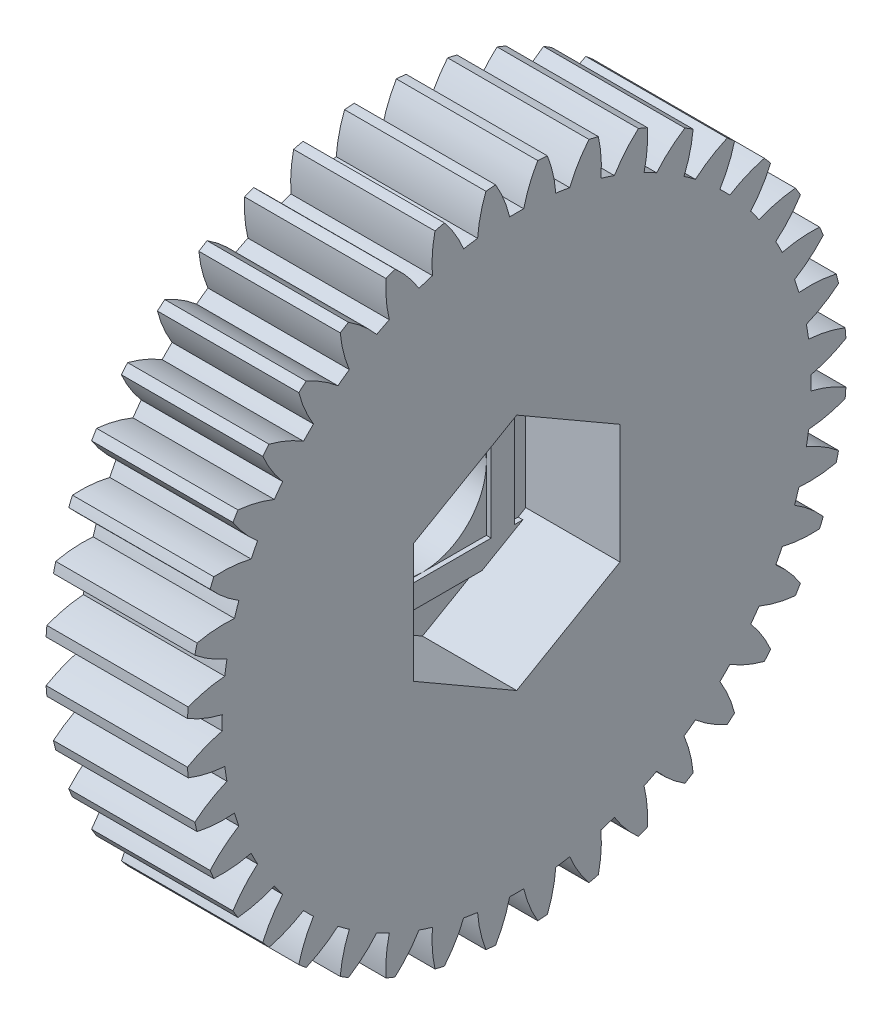
SolidWorks part; units mm, degrees
ref_plane "Plane1" through (0, 0, 0) normal (0, 0, 1) x (1, 0, 0)
ref_plane "Plane2" through (0, 0, 0) normal (0, 1, 0) x (1, 0, 0)
ref_plane "Plane3" through (0, 0, 0) normal (1, 0, 0) x (0, 0, -1)
sketch "HoldingSke" plane through (0, 0, 0) normal (0, 1, 0) x (1, 0, 0)
  line L0 (0, 0) -> (0.766, -0.6428)
  line L1 (-15, 0) -> (100, 0) construction
  line L2 (0, 0) -> (-2.1039, 2.3779)
  line L3 (0, 0) -> (-11.863, 4.5341)
  line L4 (0, 0) -> (6.6156, 5.5511)
  line L5 (0, 0) -> (-46.8476, -17.4728)
  line L6 (0, 0) -> (-7.4607, -5.0337)
  line L7 (-2.1039, 2.3779) -> (8.6586, 51.2059)
  line L8 (-76.2, 54.61) -> (-75.5, 54.61)
  line L9 (-71.009, 38.7566) -> (-53.1078, 45.2721)
  line L10 (-76.2, 71.12) -> (104.1128, 71.12)
  line L11 (0, 0) -> (-9, 0)
  line L12 (-76.2, 101.6) -> (-76.162, 101.6)
  line L13 (24.9733, 27.94) -> (52.9518, 28.4284)
  line L14 (24.9733, 27.94) -> (24.9743, 27.94)
  line L15 (24.9733, 27.94) -> (100.4006, 29.5858)
  line L16 (-63.627, -1) -> (-12.827, -1)
  circle A0 centre (0, 0) radius 2
  circle A1 centre (0, 0) radius 18.749
  circle A2 centre (0, 0) radius 37.5
  circle A3 centre (0, 0) radius 2
  dimension "MHD" = 37.498
  dimension "Hub_dia" = 75
  dimension "Bore" = 4
  dimension "MBD" = 4
  dimension "Num_teeth" = 40
  dimension "Pitch" = 1
  dimension "Overall_len" = 50
  dimension "Show_teeth" = 40
  dimension "Thickness" = 9
  dimension "OAL" = 50.0001
  dimension "T_dim" = 0.7
  dimension "Ap" = 20
  dimension "H" = 19.05
  dimension "Pitch_radius" = 180.3128
  dimension "Width" = 9
  dimension "Backlash" = 0.038
  dimension "Addendum_fac" = 1
  dimension "Dedendum_fac" = 1.25
  dimension "Clearance_fac" = 0.25
  dimension "Dedendum_add" = 0.001
  dimension "Module" = 1
sketch "BasProSke" plane through (0, 0, 0) normal (0, 1, 0) x (1, 0, 0)
  line L0 (-10, 0) -> (60, 0) construction
  line L1 (0, 0) -> (0, 21)
  line L2 (0, 0) -> (9, 0)
  line L3 (9, 0) -> (9, 21)
  line L4 (9, 21) -> (0, 21)
  dimension "Thickness" = 9
  dimension "Diameter" = 42
revolve "Base-Revolve" add sketch "BasProSke" angle 360 about L0
sketch "TooCutSke" plane through (0, 0, 0) normal (1, 0, 0) x (0, 0, -1)
  line L1 (0, 0) -> (0, 107) construction
  line L2 (0, 0) -> (-0.8517, 19.9819) construction
  line L3 (0, 0) -> (-3.1363, 39.8509) construction
  line L4 (-0.8517, 19.9819) -> (-1.5682, 19.9255) construction
  arc A0 (0.4487, 18.7436) -> (-0.4487, 18.7436) centre (0, 0) ccw
  arc A1 (1.3547, 20.9817) -> (-1.3547, 20.9817) centre (0, 0) ccw
  circle A2 centre (0, 0) radius 20 construction
  circle A3 centre (0, 0) radius 18.7939 construction
  arc A4 (-0.4487, 18.7436) -> (-1.3547, 20.9817) centre (-8.2322, 16.895) ccw
  arc A5 (1.3547, 20.9817) -> (0.4487, 18.7436) centre (8.2322, 16.895) ccw
  dimension "Root_dia" = 37.498
  dimension "Overcut_dia" = 42.0508
  dimension "Pitch_dia" = 40
  dimension "Base_dia" = 37.5877
  dimension "Flank_rad" = 8
  dimension "Half_ang" = 4.5
  dimension "Half_CT" = 0.7187
extrude "ToothCut" cut sketch "TooCutSke" along normal through all
fillet "Breaks" [suppressed] radius 0.02 tangent propagation no
fillet "RootFillets" [suppressed] radius 0.251
pattern_circular "TeethCuts" count 40 every 9 about axis through (-10, 0, 0) along (1, 0, 0) of "ToothCut", "RootFillets", "Breaks"
sketch "HubNeaOneSke" plane through (0, 0, 0) normal (-1, 0, 0) x (0, 0, 1)
  circle A0 centre (0, 0) radius 18.749
  dimension "Diameter" = 37.498
extrude "HubNearOne" [suppressed] add sketch "HubNeaOneSke" along normal blind 41.0001
sketch "HubNeaBotSke" plane through (0, 0, 0) normal (-1, 0, 0) x (0, 0, 1)
  circle A0 centre (0, 0) radius 18.749
  dimension "Diameter" = 37.498
extrude "HubNearBoth" [suppressed] add sketch "HubNeaBotSke" along normal blind 20.5001
ref_plane "FarPln" through (9, 0, 0) normal (1, 0, 0) x (0, 0, -1)
sketch "HubFarSke" plane through (9, 0, 0) normal (1, 0, 0) x (0, 0, -1)
  circle A0 centre (0, 0) radius 18.749
  dimension "Diameter" = 37.498
extrude "HubFar" [suppressed] add sketch "HubFarSke" along normal blind 20.5001
sketch "BorSke" plane through (0, 0, 0) normal (1, 0, 0) x (0, 0, -1)
  circle A0 centre (0, 0) radius 2
  dimension "Diameter" = 4
extrude "Bore" cut sketch "BorSke" along normal mid plane 100.0002
sketch "KeySke" plane through (0, 0, 0) normal (1, 0, 0) x (0, 0, -1)
  line L0 (-0.8, 0) -> (-0.8, 2.7)
  line L1 (-0.8, 2.7) -> (0.8, 2.7)
  line L2 (0.8, 2.7) -> (0.8, 0)
  line L3 (0, 0) -> (0, 34) construction
  line L4 (-0.8, 0) -> (0.8, 0)
  dimension "Offset" = 2.7
  dimension "Width" = 1.6
extrude "Keyway" [suppressed] cut sketch "KeySke" along normal mid plane 100.0002
pattern_circular "Keyway2" [suppressed] count 2 every 90 about axis through (-10, 0, 0) along (1, 0, 0) reverse direction yes
sketch "Sketch1" plane through (9, 0, 0) normal (1, 0, 0) x (0, 0, -1)
  line L1 (0, 7.5922) -> (-6.575, 3.7961)
  line L2 (-6.575, 3.7961) -> (-6.575, -3.7961)
  line L3 (-6.575, -3.7961) -> (0, -7.5922)
  line L4 (0, -7.5922) -> (6.575, -3.7961)
  line L5 (6.575, -3.7961) -> (6.575, 3.7961)
  line L6 (6.575, 3.7961) -> (0, 7.5922)
  circle A0 centre (0, 0) radius 7.5922
  circle A2 centre (0, 0) radius 6.575 construction
  circle A3 centre (0, 0) radius 4.075
  dimension "D1" = 8.15
  dimension "D2" = 13.15
extrude "Cut-Extrude1" cut sketch "Sketch1" against normal blind 6 contours L1 L2 L3 L4 L5 L6
extrude "Cut-Extrude2" cut sketch "Sketch1<7>" against normal through all contours A3 region at (9, 0, 0)
sketch "Sketch1<7>" plane through (9, 0, 0) normal (1, 0, 0) x (0, 0, -1) same geometry as "Sketch1"
sketch "Sketch2" plane through (0, 0, 0) normal (-1, 0, 0) x (0, 0, 1)
  circle A0 centre (0, 0) radius 6
  circle A1 centre (0, 0) radius 4.075
  dimension "D1" = 12
  dimension "D2" = 8.15
extrude "Boss-Extrude1" add sketch "Sketch2" along normal blind 1.8
sketch "Sketch3" plane through (3, 0, 0) normal (1, 0, 0) x (0, 0, -1)
  line L1 (4.075, 4.075) -> (-4.075, 4.075)
  line L2 (4.075, 4.075) -> (4.075, -4.075)
  line L3 (4.075, -4.075) -> (-4.075, -4.075)
  line L4 (-4.075, 4.075) -> (-4.075, -4.075)
  line L6 (5.575, 5.575) -> (5.575, -5.575)
  line L7 (5.575, -5.575) -> (-5.575, -5.575)
  line L8 (-5.575, 5.575) -> (-5.575, -5.575)
  line L9 (5.575, 5.575) -> (-5.575, 5.575)
  line L10 (5.575, 4.075) -> (6.0919, 4.075)
  line L11 (6.575, 3.7961) -> (0, 7.5922) construction
  line L12 (5.575, -4.075) -> (6.0919, -4.075)
  line L13 (0, -7.5922) -> (6.575, -3.7961) construction
  line L14 (-5.575, -4.075) -> (-6.0919, -4.075)
  line L15 (-6.575, -3.7961) -> (0, -7.5922) construction
  line L16 (-5.575, 4.075) -> (-6.0919, 4.075)
  line L17 (0, 7.5922) -> (-6.575, 3.7961) construction
  circle A0 centre (0, 0) radius 4.075 construction
  line M10 (6.575, 3.7961) -> (0, 7.5922)
  line M11 (0, 7.5922) -> (-6.575, 3.7961)
  line M13 (-6.575, -3.7961) -> (0, -7.5922)
  line M14 (0, -7.5922) -> (6.575, -3.7961)
  dimension "D1" = 1.5
extrude "Boss-Extrude2" add sketch "Sketch3" along normal blind 0.3 contours L9 L8 L7 L6 L4 L1 L2 L3 M10 M11 M13 M14 | L12 L6 M14 | L6 L10 M10 | L16 L8 M11 | L8 L14 M13 region at (3, 0, -5.4173) region at (3, 4.1745, -5.7473) region at (3, -4.1745, -5.7473) region at (3, 4.1745, 5.7473) region at (3, -4.1745, 5.7473)
equation "' \"Module@HoldingSke\" = 6.35"
equation "' \"Num_teeth@HoldingSke\" = 12"
equation "' \"Ap@HoldingSke\" =  20"
equation "' \"Ap@HoldingSke\" = 20"
equation "' \"Width@HoldingSke\" = 0.5 * 25.4"
equation "' \"Hub_dia@HoldingSke\"= 1 * 25.4"
equation "' \"Hub_dia@HoldingSke\" = 1 * 25.4"
equation "' \"Overall_len@HoldingSke\" = 1.0 * 25.4"
equation "' \"Bore@HoldingSke\" = 0.75 * 25.4"
equation "' \"T_dim@HoldingSke\" = 0.1 * 25.4"
equation "' \"Width@KeySke\" = 0.25 * 25.4"
equation "' \"Show_teeth@HoldingSke\" = 13"
equation "' \"Backlash@HoldingSke\" = 0.009 * 25.4"
equation "' \"Addendum_fac@HoldingSke\" = 1.0"
equation "' \"Dedendum_fac@HoldingSke\" = 1.25"
equation "' \"Dedendum_add@HoldingSke\" = 0.00005 * 25.4"
equation "' \"Clearance_fac@HoldingSke\" = 0.25"
equation "\"Pitch@HoldingSke\" = 1 / \"Module@HoldingSke\""
equation "\"Overcut_dia@TooCutSke\" = (\"Num_teeth@HoldingSke\" + 2 * \"Addendum_fac@HoldingSke\") / \"Pitch@HoldingSke\" + 0.002 * 25.4"
equation "\"Pitch_dia@TooCutSke\" = \"Num_teeth@HoldingSke\" / \"Pitch@HoldingSke\""
equation "\"Base_dia@TooCutSke\" = \"Num_teeth@HoldingSke\" / \"Pitch@HoldingSke\" * cos((\"Ap@HoldingSke\"  * 3.14159265 / 180))"
equation "\"Root_dia@TooCutSke\" = (\"Num_teeth@HoldingSke\" + 2) / \"Pitch@HoldingSke\" - 2 * (\"Addendum_fac@HoldingSke\" + \"Dedendum_fac@HoldingSke\") / \"Pitch@HoldingSke\" - \"Dedendum_add@HoldingSke\" * 2"
equation "\"Half_ang@TooCutSke\" = 180 / \"Num_teeth@HoldingSke\""
equation "\"Half_CT@TooCutSke\" = \"Num_teeth@HoldingSke\" / \"Pitch@HoldingSke\" * sin((3.14159265 / 2 / \"Num_teeth@HoldingSke\")) / 2 - 7 * \"Backlash@HoldingSke\" / 4"
equation "\"Flank_rad@TooCutSke\" = \"Num_teeth@HoldingSke\" / \"Pitch@HoldingSke\" / 5"
equation "\"Radius@RootFillets\" = \"Clearance_fac@HoldingSke\" / \"Pitch@HoldingSke\" + \"Dedendum_add@HoldingSke\""
equation "\"Break_rad@Breaks\" = 0.02 / \"Pitch@HoldingSke\""
equation "\"Thickness@HoldingSke\" = \"Width@HoldingSke\""
equation "\"OAL@HoldingSke\" = \"Thickness@HoldingSke\""
equation "\"MHD@HoldingSke\" = (\"Num_teeth@HoldingSke\" + 2) / \"Pitch@HoldingSke\" - 2 * (\"Addendum_fac@HoldingSke\" + \"Dedendum_fac@HoldingSke\")  / \"Pitch@HoldingSke\" - \"Dedendum_add@HoldingSke\" * 2"
equation "\"MBD@HoldingSke\" = (\"Num_teeth@HoldingSke\" + 2) / \"Pitch@HoldingSke\" - 2 * (\"Addendum_fac@HoldingSke\" + \"Dedendum_fac@HoldingSke\")  / \"Pitch@HoldingSke\" - \"Dedendum_add@HoldingSke\" * 2 - 0.002 * 25.4"
equation "\"MHD@HoldingSke\" = ((sgn( \"MHD@HoldingSke\" - \"Hub_dia@HoldingSke\" )-1)*( \"MHD@HoldingSke\" - \"Hub_dia@HoldingSke\" ))/-2+ \"Hub_dia@HoldingSke\""
equation "\"MBD@HoldingSke\" = ((sgn( \"MBD@HoldingSke\" - \"Bore@HoldingSke\" )-1)*( \"MBD@HoldingSke\" - \"Bore@HoldingSke\" ))/-2+ \"Bore@HoldingSke\""
equation "\"OAL@HoldingSke\" = ((sgn( \"OAL@HoldingSke\" - \"Overall_len@HoldingSke\" )+1)*( \"OAL@HoldingSke\" - \"Overall_len@HoldingSke\" ))/2 + \"Overall_len@HoldingSke\" + 0.000002 * 25.4"
equation "\"Num_teeth@TeethCuts\" = int( \"Show_teeth@HoldingSke\" ) + 1"
equation "\"Num_teeth@TeethCuts\" = ((sgn( \"Num_teeth@TeethCuts\" - \"Num_teeth@HoldingSke\" )-1)*( \"Num_teeth@TeethCuts\" - \"Num_teeth@HoldingSke\" ))/-2+ \"Num_teeth@HoldingSke\""
equation "\"Num_teeth@TeethCuts\" = ((sgn( \"Num_teeth@TeethCuts\" - 2.0)+1)*( \"Num_teeth@TeethCuts\" - 2.0))/2 +2.0"
equation "\"Angle@TeethCuts\" = 360.0 / \"Num_teeth@HoldingSke\""
equation "\"Diameter@BasProSke\" = (\"Num_teeth@HoldingSke\" + 2 * \"Addendum_fac@HoldingSke\") / \"Pitch@HoldingSke\""
equation "\"Thickness@BasProSke\"  = \"Thickness@HoldingSke\""
equation "' \"Fillet_rad@BasProSke\" =  \"Thickness@HoldingSke\" * 0.05"
equation "' \"Fillet_rad@BasProSke\" = \"Thickness@HoldingSke\" * 0.05"
equation "\"MHD@HoldingSke\" = ((sgn( \"MHD@HoldingSke\" - \"Root_dia@TooCutSke\" )-1)*( \"MHD@HoldingSke\" - \"Root_dia@TooCutSke\" ))/-2+ \"Root_dia@TooCutSke\""
equation "\"Diameter@HubNeaOneSke\" = \"MHD@HoldingSke\""
equation "\"Length@HubNearOne\" = \"OAL@HoldingSke\" - \"Thickness@BasProSke\""
equation "\"Diameter@HubNeaBotSke\" = \"MHD@HoldingSke\""
equation "\"Length@HubNearBoth\" = ( \"OAL@HoldingSke\" - \"Thickness@BasProSke\" ) / 2.0"
equation "\"Thickness@FarPln\" = \"Thickness@BasProSke\""
equation "\"Diameter@HubFarSke\" = \"MHD@HoldingSke\""
equation "\"Length@HubFar\" = ( \"OAL@HoldingSke\" - \"Thickness@BasProSke\" ) / 2.0"
equation "\"Diameter@BorSke\" = \"MBD@HoldingSke\""
equation "\"D1@Bore\" = \"OAL@HoldingSke\" * 2.0"
equation "\"D1@Keyway\" = \"OAL@HoldingSke\" * 2.0"
equation "\"Offset@KeySke\" = \"T_dim@HoldingSke\" + \"MBD@HoldingSke\" / 2.0"
equation "\"shaft_diameter\"= 8.15"
equation "\"D1@Sketch1\"=\"shaft_diameter\""
equation "\"D2@Sketch2\"=\"shaft_diameter\""
equation "\"bolt_head\"=13.15"
equation "\"D2@Sketch1\"=\"bolt_head\""
